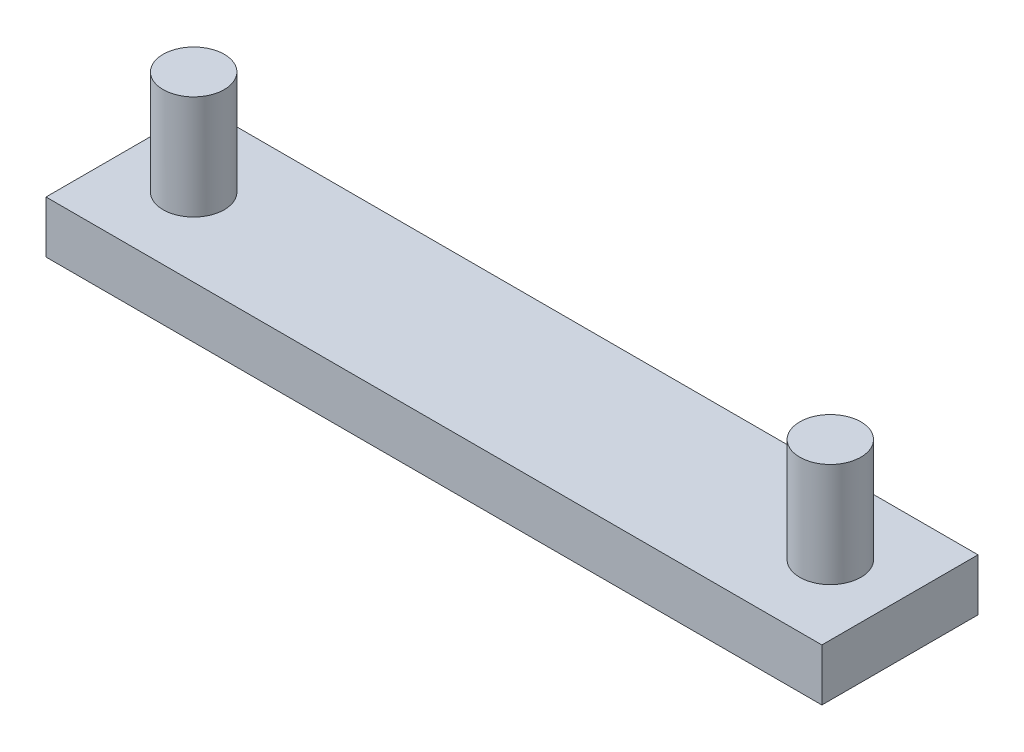
SolidWorks part; units mm, degrees
material "1060 Alloy"
ref_plane "Front Plane" through (0, 0, 0) normal (0, 0, 1) x (1, 0, 0)
ref_plane "Top Plane" through (0, 0, 0) normal (0, 1, 0) x (1, 0, 0)
ref_plane "Right Plane" through (0, 0, 0) normal (1, 0, 0) x (0, 0, -1)
sketch "Sketch1" plane through (0, 0, 0) normal (0, 1, 0) x (1, 0, 0)
  line L0 (29.86, 0) -> (67.96, 0)
  line L1 (67.96, 0) -> (67.96, 76.2)
  line L2 (67.96, 0) -> (67.96, -76.2)
  line L3 (0, 0) -> (-621.47, 0)
  line L4 (-651.33, 0) -> (-689.43, 0)
  line L5 (-689.43, 0) -> (-689.43, 76.2)
  line L7 (-689.43, 76.2) -> (67.96, 76.2)
  line L8 (-689.43, 76.2) -> (-689.43, -76.2)
  line L9 (-689.43, -76.2) -> (67.96, -76.2)
  line L10 (67.96, 76.2) -> (67.96, -76.2)
  circle A0 centre (0, 0) radius 29.86
  circle A1 centre (-621.47, 0) radius 29.86
  dimension "D1" = 59.72
  dimension "D6" = 59.72
  dimension "D3" = 76.2
  dimension "D4" = 38.1
  dimension "D5" = 621.47
  dimension "D7" = 38.1
  dimension "D8" = 76.2
extrude "Boss-Extrude1" add sketch "Sketch1" along normal blind 50.8 contours A1 L4 L8 L9 L2 L0 A0 L3 | A1 L3 A0 L0 L1 L7 L5 L4 region at (-310.735, 0, -39.3971) region at (-310.735, 0, 39.3971)
sketch "Sketch2" plane through (0, 0, 0) normal (0, -1, 0) x (1, 0, 0)
  circle A0 centre (0, 0) radius 29.86 construction
  circle A1 centre (0, 0) radius 29.86
  circle A2 centre (-621.47, 0) radius 29.86 construction
  circle A3 centre (-621.47, 0) radius 29.86
extrude "Boss-Extrude2" add sketch "Sketch2" against normal blind 152.4
